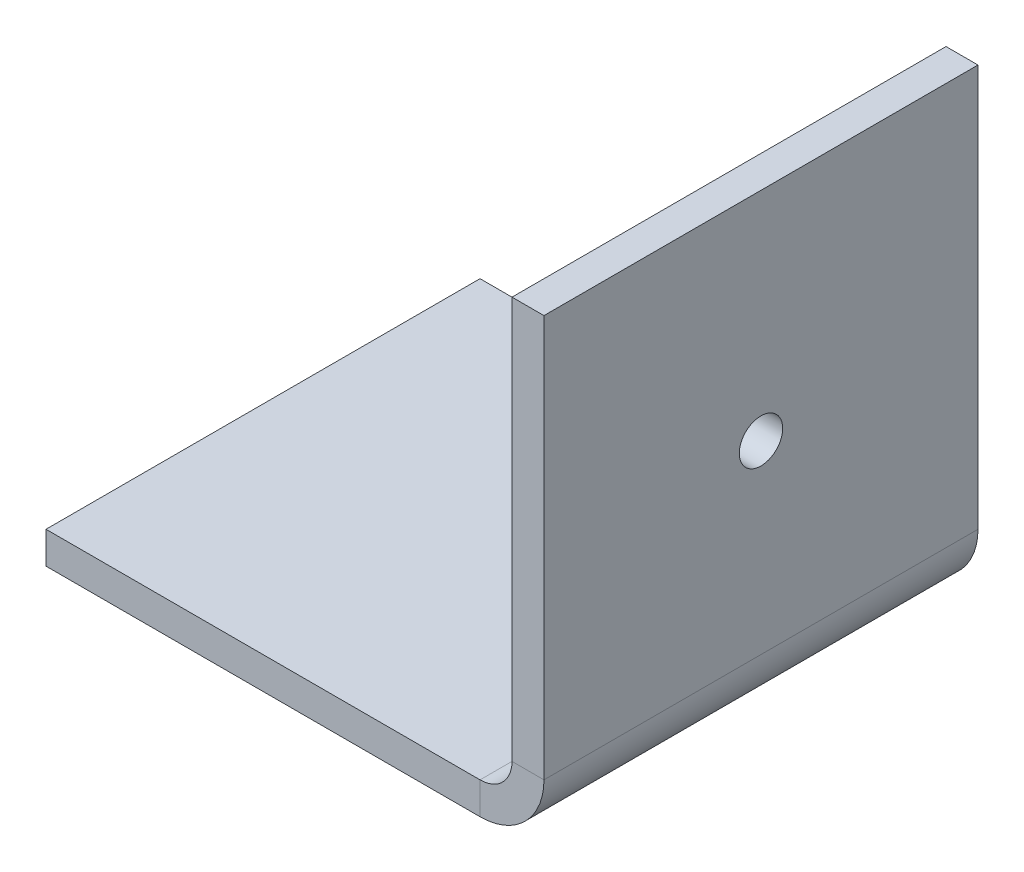
SolidWorks part; units mm, degrees
note: The reader was unsure of these and kept them because the rebuilt part matched: flange length of "Edge-Flange1".
ref_plane "Front Plane" through (0, 0, 0) normal (0, 0, 1) x (1, 0, 0)
ref_plane "Top Plane" through (0, 0, 0) normal (0, 1, 0) x (1, 0, 0)
ref_plane "Right Plane" through (0, 0, 0) normal (1, 0, 0) x (0, 0, -1)
sketch "Sketch1" plane through (0, 0, 0) normal (0, 1, 0) x (1, 0, 0)
  line L1 (-5, 5) -> (5, 5)
  line L2 (-5, 5) -> (-5, -5)
  line L3 (-5, -5) -> (5, -5)
  line L4 (5, 5) -> (5, -5)
  line L5 (-5, 5) -> (5, -5) construction
  line L6 (-5, -5) -> (5, 5) construction
  point P0 (0, 0)
  dimension "D1" = 10
  dimension "D2" = 10
base flange "Base-Flange1" sketch "Sketch1" thickness 0.7366 reverse thickness direction no parameters "D1"=0.7366
edge flange "Edge-Flange1" sketch "Sketch8" flange angle 90 flange length 10 flange position bend outside bend radius 0.7366 thickness 0.7366 relief rectangular parameters "D6"=10
sketch "Sketch8" plane through (5, 0, 0) normal (1, 0, 0) x (0, 0, -1)
  line L0 (-5, 0) -> (5, 0) construction
  line L1 (-5, 0) -> (5, 0)
  line L2 (-5, 0) -> (-5, 10)
  line L3 (-5, 10) -> (5, 10)
  line L4 (5, 10) -> (5, 0)
  line L5 (0, 10) -> (0, 0) construction
  line L6 (5, 5) -> (-5, 5) construction
  circle A0 centre (0, 5) radius 0.5
  dimension "D2" = 1
  dimension "D1" = 10
bend "EdgeBend1" bend radius 0.7366 bend angle 90 parameters "D5"=1
sketch "Bend-Lines1" plane through (0, 0, 0) normal (0, 1, 0) x (1, 0, 0)
sketch "Bounding-Box1" plane through (0, 0, 0) normal (0, 1, 0) x (1, 0, 0)
sheet metal parameters "Sheet-Metal(1)" thickness 0.7366 parameters "D1"=0.7366
flat pattern "Flat-Pattern(1)" [suppressed]
sketch "Bend-Lines2" plane through (0, 0, 0) normal (0, 1, 0) x (1, 0, 0)
sketch "Bounding-Box2" [suppressed] plane through (0, 0, 0) normal (0, 1, 0) x (1, 0, 0)
sheet metal parameters "Sheet-Metal(2)" thickness 0.7366 parameters "D1"=0.7366
flat pattern "Flat-Pattern(1)" [suppressed]
sketch "Bend-Lines3" plane through (0, 0, 0) normal (0, 1, 0) x (1, 0, 0)
sketch "Bounding-Box3" [suppressed] plane through (0, 0, 0) normal (0, 1, 0) x (1, 0, 0)
bend of the flat pattern "Flatten-<EdgeBend1>1"
